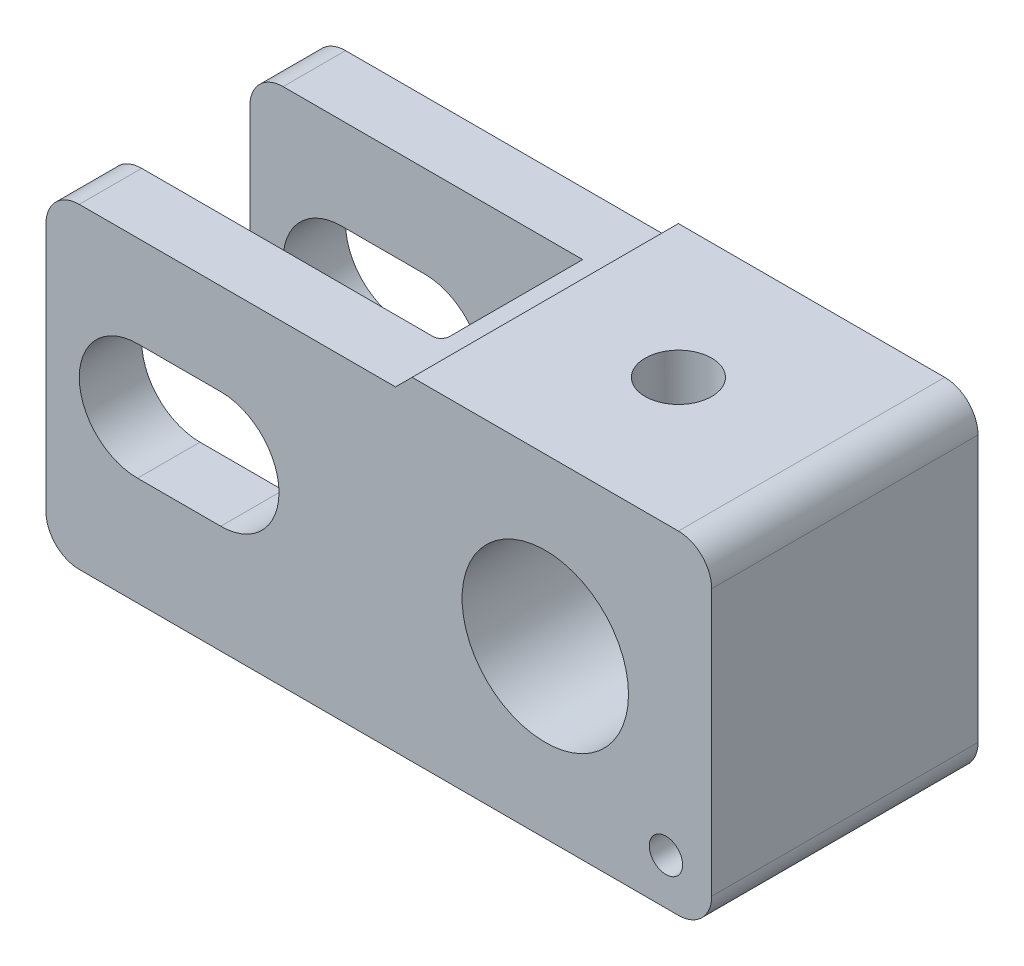
SolidWorks part; units mm, degrees
ref_plane "前视基准面" through (0, 0, 0) normal (0, 0, 1) x (1, 0, 0)
ref_plane "上视基准面" through (0, 0, 0) normal (0, 1, 0) x (1, 0, 0)
ref_plane "右视基准面" through (0, 0, 0) normal (1, 0, 0) x (0, 0, -1)
sketch "草图1" plane through (0, 0, 0) normal (0, 0, 1) x (1, 0, 0)
  line L0 (-10, -10) -> (-10, 9) construction
  line L1 (-10, -10) -> (10, -10)
  line L2 (-10, 9) -> (-10, 10) construction
  line L3 (-8, 10) -> (10, 10)
  line L4 (10, -10) -> (10, 10)
  line L5 (-10, -10) -> (10, 10) construction
  line L6 (-9, 9) -> (10, -10) construction
  line L7 (-10, -10) -> (-30, -10)
  line L8 (-10, -10) -> (-10, 9) construction
  line L9 (-10, 9) -> (-30, 9)
  line L10 (-30, -10) -> (-30, 9)
  line L11 (-10, 9) -> (-8, 9)
  line L12 (-8, 9) -> (-8, 10)
  line L13 (-10, 10) -> (-8, 10) construction
  line L14 (-10, 10) -> (-9, 9) construction
  line L15 (-24.5, 0) -> (-19.5, 0) construction
  line L16 (55, 0) -> (-55, 0) construction
  line L17 (-24.5, 3.5) -> (-19.5, 3.5)
  line L18 (-24.5, -3.5) -> (-19.5, -3.5)
  circle A0 centre (0, 0) radius 5
  arc A1 (-24.5, 3.5) -> (-24.5, -3.5) centre (-24.5, 0) ccw
  arc A2 (-19.5, -3.5) -> (-19.5, 3.5) centre (-19.5, 0) ccw
  point P17 (-22, 0)
  dimension "D1" = 10
  dimension "D7" = 12
  dimension "D9" = 2
  dimension "D2" = 20
  dimension "D3" = 19
  dimension "D4" = 20
  dimension "D5" = 2
  dimension "D6" = 40
  dimension "D8" = 7
extrude "凸台-拉伸1" add sketch "草图1" along normal mid plane 16
chamfer "倒角1" distance 1 angle 45 1 edges at (-8, 9, 0)
fillet "圆角1" radius 2 4 edges at (10, -10, 0) (-30, -10, 0) (10, 10, 0) (-30, 9, 0)
sketch "草图2" plane through (0, 9, 0) normal (0, 1, 0) x (1, 0, 0)
  line L0 (-11, 0) -> (11, 0) construction
  line L1 (-10, -4.25) -> (-30, -4.25)
  line L2 (-10, -4.25) -> (-10, 4.25)
  line L3 (-10, 4.25) -> (-30, 4.25)
  line L4 (-30, -4.25) -> (-30, 4.25)
  line L5 (-10, -4.25) -> (-30, 4.25) construction
  line L6 (-10, 4.25) -> (-30, -4.25) construction
  line L7 (-30, -8) -> (-30, 8) construction
  point P0 (-20, 0)
  dimension "D1" = 8.5
  dimension "D2" = 20
extrude "切除-拉伸1" cut sketch "草图2" against normal through all
sketch "草图3" plane through (0, 0, 8) normal (0, 0, 1) x (1, 0, 0)
  line L0 (-28, -10) -> (8, -10) construction
  line L1 (10, -8) -> (10, 8) construction
  circle A0 centre (7.25, -7.25) radius 1
  dimension "D1" = 2
  dimension "D2" = 2.75
  dimension "D3" = 2.75
extrude "切除-拉伸2" cut sketch "草图3" against normal through all
fillet "圆角2" radius 0.5 1 edges at (-10, -0.5, 4.25)
sketch "草图4" plane through (0, 10, 0) normal (0, 1, 0) x (1, 0, 0)
  circle A0 centre (0, 0) radius 2
  dimension "D1" = 4
extrude "切除-拉伸3" cut sketch "草图4" against normal through all
